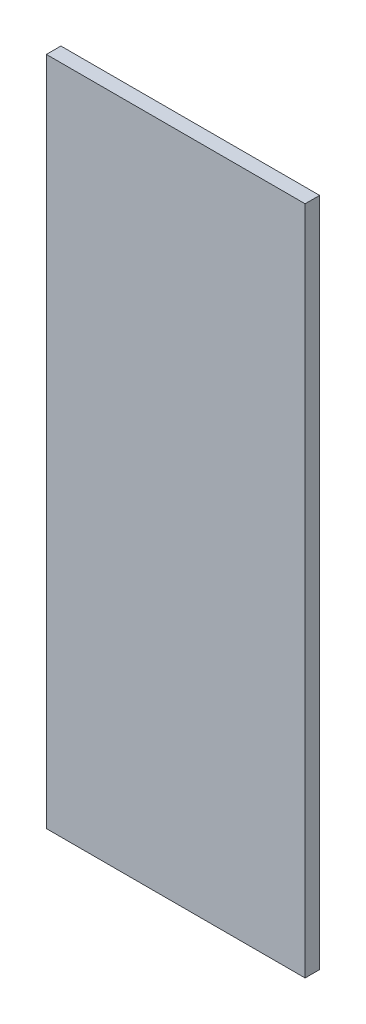
SolidWorks part; units mm, degrees
material "ABS"
ref_plane "X-Y Datum" through (0, 0, 0) normal (0, 0, 1) x (1, 0, 0)
ref_plane "X-Z Datum" through (0, 0, 0) normal (0, 1, 0) x (1, 0, 0)
ref_plane "Y-Z Datum" through (0, 0, 0) normal (1, 0, 0) x (0, 0, -1)
sketch "Sketch1" plane through (0, 0, 0) normal (0, 0, 1) x (1, 0, 0)
  line L1 (-28.275, 73.275) -> (28.275, 73.275)
  line L2 (-28.275, 73.275) -> (-28.275, -73.275)
  line L3 (-28.275, -73.275) -> (28.275, -73.275)
  line L4 (28.275, 73.275) -> (28.275, -73.275)
  line L5 (-28.275, 73.275) -> (28.275, -73.275) construction
  line L6 (-28.275, -73.275) -> (28.275, 73.275) construction
  point P0 (0, 0)
  dimension "D1" = 56.55
  dimension "D2" = 146.55
extrude "Boss-Extrude1" add sketch "Sketch1" along normal blind 3.175
